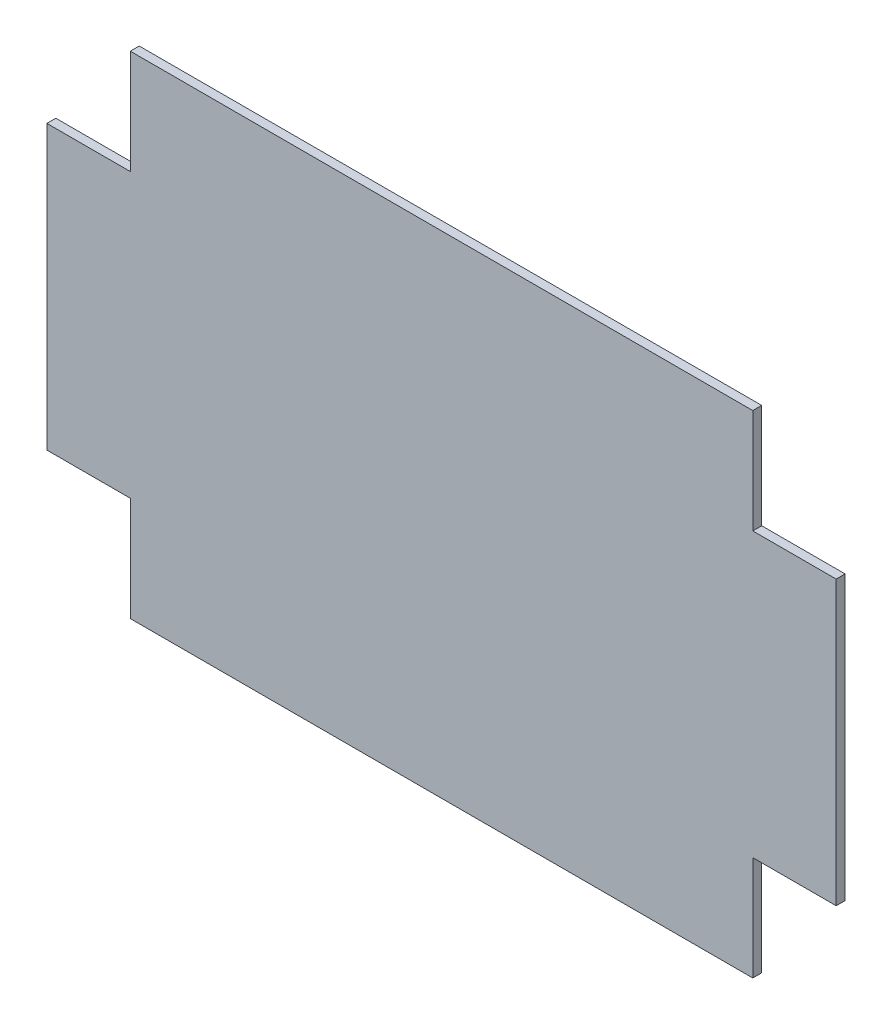
SolidWorks part; units mm, degrees
ref_plane "Front Plane" through (0, 0, 0) normal (0, 0, 1) x (1, 0, 0)
ref_plane "Top Plane" through (0, 0, 0) normal (0, 1, 0) x (1, 0, 0)
ref_plane "Right Plane" through (0, 0, 0) normal (1, 0, 0) x (0, 0, -1)
sketch "Sketch1" plane through (0, 0, 0) normal (0, 0, 1) x (1, 0, 0)
  line L0 (-132.5, 0) -> (0, 0) construction
  line L1 (0, 0) -> (0, 82.5) construction
  line L2 (104.5, 82.5) -> (-104.5, 82.5)
  line L3 (-132.5, 47.5) -> (-132.5, -47.5)
  line L4 (-132.5, 47.5) -> (-104.5, 47.5)
  line L5 (-104.5, 47.5) -> (-104.5, 82.5)
  line L6 (132.5, 47.5) -> (104.5, 47.5)
  line L7 (132.5, 47.5) -> (132.5, -47.5)
  line L8 (104.5, 47.5) -> (104.5, 82.5)
  line L9 (132.5, -47.5) -> (104.5, -47.5)
  line L10 (104.5, -47.5) -> (104.5, -82.5)
  line L11 (104.5, -82.5) -> (-104.5, -82.5)
  line L12 (-104.5, -47.5) -> (-104.5, -82.5)
  line L13 (-132.5, -47.5) -> (-104.5, -47.5)
  point P12 (132.5, 0)
  dimension "D1" = 132.5
  dimension "D2" = 82.5
  dimension "D3" = 28
  dimension "D4" = 35
extrude "Boss-Extrude1" add sketch "Sketch1" along normal blind 3
sketch "Sketch2" plane through (0, 0, 3) normal (0, 0, 1) x (1, 0, 0)
  line L0 (0, -99.6976) -> (0, 95.9822) construction
  point P3 (0, -99.6976)
ref_axis "Axis1" through (0, -99.6976, 3) along (0, 1, 0)
